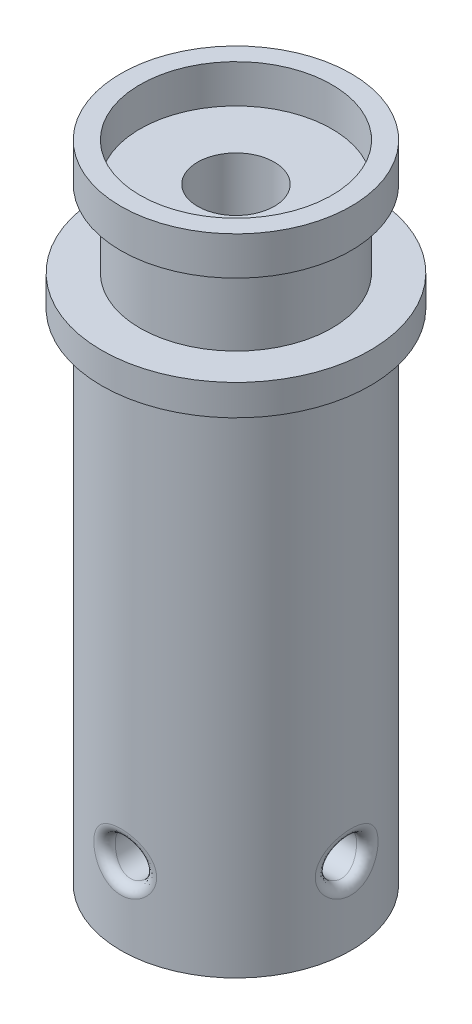
SolidWorks part; units mm, degrees
ref_plane "Front Plane" through (0, 0, 0) normal (0, 0, 1) x (1, 0, 0)
ref_plane "Top Plane" through (0, 0, 0) normal (0, 1, 0) x (1, 0, 0)
ref_plane "Right Plane" through (0, 0, 0) normal (1, 0, 0) x (0, 0, -1)
sketch "Sketch1" plane through (0, 0, 0) normal (0, 1, 0) x (1, 0, 0)
  line L0 (0, 0) -> (-13523.7469, 0) construction
  line L1 (0, 0) -> (0, 13523.7469) construction
  line L2 (7, 0) -> (44203.7332, -23380.5212) construction
  circle A0 centre (0, 0) radius 6
  dimension "D1" = 12
extrude "Boss-Extrude1" add sketch "Sketch1" along normal blind 12
sketch "Sketch2" plane through (0, 12, 0) normal (0, 1, 0) x (1, 0, 0)
  circle A0 centre (0, 0) radius 6
  dimension "D1" = 12
extrude "Boss-Extrude2" add sketch "Sketch2" along normal blind 14
sketch "Sketch3" plane through (0, 26, 0) normal (0, 1, 0) x (1, 0, 0)
  circle A0 centre (0, 0) radius 7
  dimension "D1" = 14
extrude "Boss-Extrude3" add sketch "Sketch3" along normal blind 1.6
sketch "Sketch4" plane through (0, 27.6, 0) normal (0, 1, 0) x (1, 0, 0)
  circle A0 centre (0, 0) radius 5
  dimension "D1" = 10
extrude "Boss-Extrude4" add sketch "Sketch4" along normal blind 4
sketch "Sketch5" plane through (0, 31.6, 0) normal (0, 1, 0) x (1, 0, 0)
  circle A0 centre (0, 0) radius 2
  dimension "D1" = 4
extrude "Cut-Extrude1" cut sketch "Sketch5" against normal through all
sketch "Sketch6" plane through (0, 0, 0) normal (0, -1, 0) x (1, 0, 0)
  circle A0 centre (0, 0) radius 3
  dimension "D1" = 6
extrude "Cut-Extrude2" cut sketch "Sketch6" against normal blind 20
sketch "Sketch7" plane through (0, 0, 0) normal (0, -1, 0) x (1, 0, 0)
  line L0 (0, 3) -> (0, 6) construction
  circle A0 centre (0, 0) radius 3 construction
  circle A1 centre (0, 0) radius 6 construction
ref_plane "Plane1" through (0, 0, 6) normal (0, 0, 1) x (1, 0, 0)
sketch "Sketch8" plane through (0, 0, 6) normal (0, 0, 1) x (1, 0, 0)
  line L0 (0, 0) -> (0, 50000) construction
  circle A0 centre (0, 4) radius 1
  dimension "D1" = 2
extrude "Cut-Extrude3" cut sketch "Sketch8" against normal up to next
pattern_circular "CirPattern1" count 2 every 90 about axis through (0, 0, 0) along (0, 1, 0) of "Cut-Extrude3"
fillet "Fillet1" radius 0.5 2 edges at (5.92, 3.7855, 0.9767) (-0.9767, 3.7855, 5.92)
sketch "Sketch9" plane through (0, 31.6, 0) normal (0, 1, 0) x (1, 0, 0)
  circle A0 centre (0, 0) radius 6
  circle A2 centre (0, 0) radius 5
  dimension "D1" = 12
  dimension "D2" = 10
extrude "Boss-Extrude5" add sketch "Sketch9" along normal blind 2 separate body
extrude "Boss-Extrude6" add sketch "Sketch9<2>" against normal blind 2 from offset 19.6 offset against normal yes
sketch "Sketch9<2>" plane through (0, 31.6, 0) normal (0, 1, 0) x (1, 0, 0) same geometry as "Sketch9"
extrude "Boss-Extrude7" add sketch "Sketch9<3>" against normal blind 1 from offset 10.8 offset against normal yes
sketch "Sketch9<3>" plane through (0, 31.6, 0) normal (0, 1, 0) x (1, 0, 0) same geometry as "Sketch9"
extrude "Boss-Extrude8" add sketch "Sketch9<4>" along normal blind 1 from offset 8.8 offset against normal yes
sketch "Sketch9<4>" plane through (0, 31.6, 0) normal (0, 1, 0) x (1, 0, 0) same geometry as "Sketch9"
